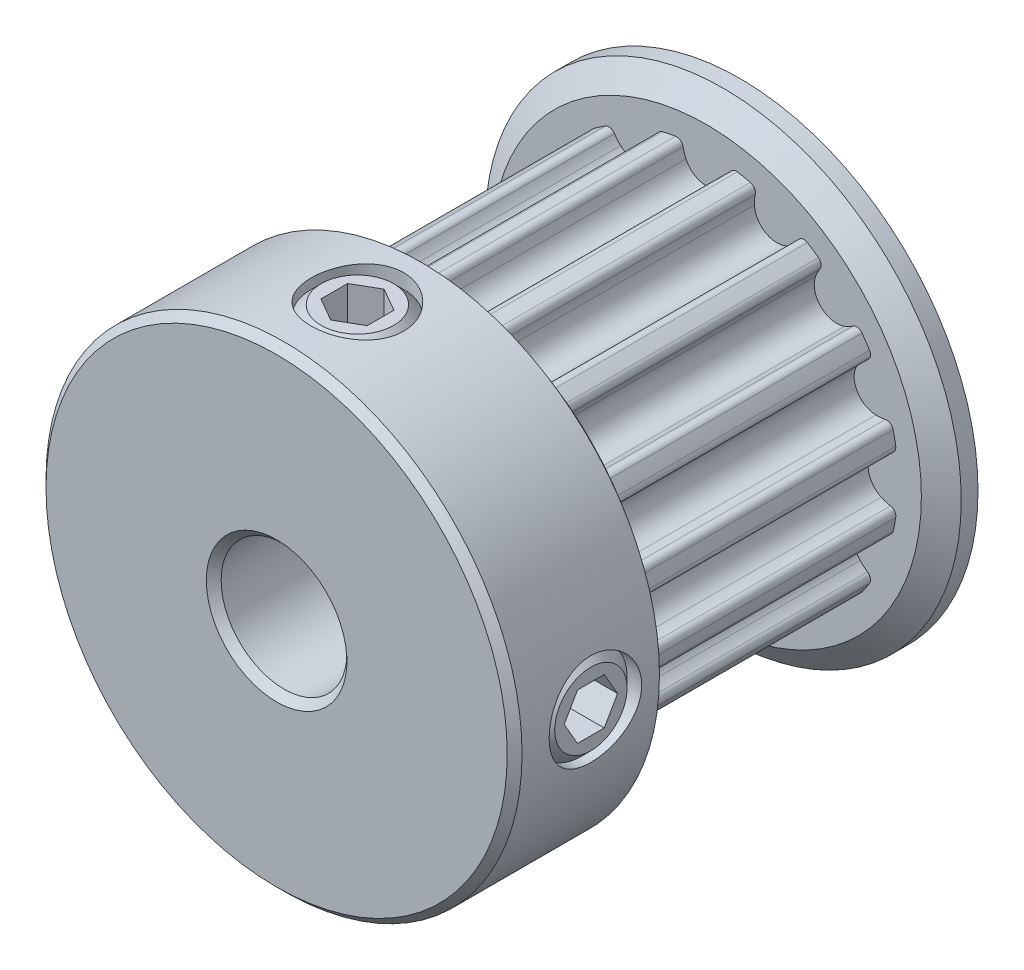
SolidWorks part; units mm, degrees
ref_plane "Front Plane" through (0, 0, 0) normal (0, 0, 1) x (1, 0, 0)
ref_plane "Top Plane" through (0, 0, 0) normal (0, 1, 0) x (1, 0, 0)
ref_plane "Right Plane" through (0, 0, 0) normal (1, 0, 0) x (0, 0, -1)
sketch "Sketch1" plane through (0, 0, 0) normal (0, 0, 1) x (1, 0, 0)
  line L1 (-2.553, 6.1245) -> (2.553, 6.1245) construction
  line L4 (0, 0) -> (0, 6.1245) construction
  line L5 (0, 6.1245) -> (0, 12.0266) construction
  line L6 (0, 7.6455) -> (2.9417, 7.0569) construction
  line L7 (2.9417, 7.0569) -> (3.8741, 6.6682) construction
  line L8 (2.9417, 7.0569) -> (2.553, 6.1245) construction
  line L9 (-2.9417, 7.0569) -> (-2.553, 6.1245) construction
  line L10 (-2.7951, 6.7052) -> (-3.7579, 9.015)
  line L11 (-3.7579, 9.015) -> (3.7579, 9.015)
  line L12 (3.7579, 9.015) -> (2.7951, 6.7052)
  circle A0 centre (0, 0) radius 7.6455 construction
  circle A1 centre (0, 0) radius 9.015 construction
  circle A2 centre (0, 0) radius 7.2645 construction
  arc A3 (-0.7739, 6.6229) -> (0.7739, 6.6229) centre (0, 6.9745) ccw
  arc A4 (-0.7739, 6.6229) -> (-0.8836, 6.9694) centre (0.61, 7.2516) cw
  arc A5 (-2.7951, 6.7052) -> (-1.1695, 7.1697) centre (0, 0) cw
  arc A6 (-0.8836, 6.9694) -> (-1.1695, 7.1697) centre (-1.1292, 6.923) ccw
  arc A7 (2.7951, 6.7052) -> (1.1695, 7.1697) centre (0, 0) ccw
  arc A8 (0.8836, 6.9694) -> (1.1695, 7.1697) centre (1.1292, 6.923) cw
  arc A9 (0.7739, 6.6229) -> (0.8836, 6.9694) centre (-0.61, 7.2516) ccw
  point P6 (0, 20.9083)
  point P11 (0, 7.6455)
  point P13 (0, 9.015)
  point P14 (0, 7.2645)
  dimension "D1" = 8.8817
  dimension "D2" = 4.3811
sketch "Sketch2" plane through (0, 0, 0) normal (1, 0, 0) x (0, 0, -1)
  line L0 (-8.775, 2.3812) -> (8.775, 2.3812)
  line L1 (-8.775, 2.3812) -> (-8.775, 9.015)
  line L2 (-3.29, 9.015) -> (-8.775, 9.015)
  line L3 (-3.925, 2.3813) -> (-3.925, 9.015) construction
  line L4 (-3.925, 9.015) -> (-2.655, 9.015) construction
  line L5 (-2.655, 9.015) -> (-2.655, 7.2645) construction
  line L6 (-2.655, 7.2645) -> (7.505, 7.2645)
  line L7 (7.505, 7.2645) -> (7.505, 9.015) construction
  line L8 (7.505, 9.015) -> (8.775, 9.015) construction
  line L9 (8.775, 9.015) -> (8.775, 2.3812)
  line L10 (-8.775, 0) -> (8.775, 0) construction
  line L11 (8.14, 9.015) -> (7.505, 8.1398)
  line L12 (-2.655, 8.1398) -> (-3.29, 9.015)
  line L14 (-2.655, 8.1398) -> (-2.655, 7.2645)
  line L15 (7.505, 7.2645) -> (7.505, 8.1398)
  line L16 (8.14, 9.015) -> (8.775, 9.015)
  arc A0 (-2.655, 8.1398) -> (-3.29, 9.015) centre (-3.5757, 8.1398) ccw construction
  arc A1 (7.505, 8.1398) -> (8.14, 9.015) centre (8.4257, 8.1398) cw construction
  point P12 (-2.655, 8.1398)
  point P14 (-3.29, 9.015)
  point P20 (7.505, 8.1398)
  point P21 (8.14, 9.015)
  point P25 (7.505, 0)
  point P26 (-2.655, 0)
  dimension "OA" = 17.55
  dimension "Bore" = 4.7625
  dimension "Outside Width" = 11.43
  dimension "Inside Width" = 10.16
revolve "Revolve1" add sketch "Sketch2" angle 360 mid plane about L10
sketch "Sketch3" plane through (0, 0, 0) normal (0, 0, 1) x (1, 0, 0)
  line L6 (3.7579, 9.015) -> (-3.7579, 9.015)
  line L7 (2.7951, 6.7052) -> (3.7579, 9.015)
  line L8 (-3.7579, 9.015) -> (-2.7951, 6.7052)
  line L9 (3.7579, 9.015) -> (-3.7579, 9.015)
  line L10 (2.7951, 6.7052) -> (3.7579, 9.015)
  line L11 (-3.7579, 9.015) -> (-2.7951, 6.7052)
  arc A8 (2.7951, 6.7052) -> (1.1695, 7.1697) centre (0, 0) ccw
  arc A9 (1.1695, 7.1697) -> (0.8836, 6.9694) centre (1.1292, 6.923) ccw
  arc A10 (0.7739, 6.6229) -> (0.8836, 6.9694) centre (-0.61, 7.2516) ccw
  arc A11 (-0.7739, 6.6229) -> (0.7739, 6.6229) centre (0, 6.9745) ccw
  arc A12 (-0.8836, 6.9694) -> (-0.7739, 6.6229) centre (0.61, 7.2516) ccw
  arc A13 (-0.8836, 6.9694) -> (-1.1695, 7.1697) centre (-1.1292, 6.923) ccw
  arc A14 (-1.1695, 7.1697) -> (-2.7951, 6.7052) centre (0, 0) ccw
  arc A15 (2.7951, 6.7052) -> (1.1695, 7.1697) centre (0, 0) ccw
  arc A16 (1.1695, 7.1697) -> (0.8836, 6.9694) centre (1.1292, 6.923) ccw
  arc A17 (0.7739, 6.6229) -> (0.8836, 6.9694) centre (-0.61, 7.2516) ccw
  arc A18 (-0.7739, 6.6229) -> (0.7739, 6.6229) centre (0, 6.9745) ccw
  arc A19 (-0.8836, 6.9694) -> (-0.7739, 6.6229) centre (0.61, 7.2516) ccw
  arc A20 (-0.8836, 6.9694) -> (-1.1695, 7.1697) centre (-1.1292, 6.923) ccw
  arc A21 (-1.1695, 7.1697) -> (-2.7951, 6.7052) centre (0, 0) ccw
  dimension "D1" = 0
extrude "Cut-Extrude1" cut sketch "Sketch3" against normal up to vertex (7.505 mm away) from vertex up to point (0, 7.2645, -7.505) starting at point (0, 7.2645, 2.655)
pattern_circular "CirPattern1" count 16 over 360 about axis through (0, 0, 8.775) along (0, 0, 1) of "Cut-Extrude1"
sketch "Sketch4" plane through (0, 0, 0) normal (1, 0, 0) x (0, -1, 0)
  line L0 (0, -2.655) -> (0, -8.775) construction
  line L1 (-2.3812, -8.775) -> (2.3812, -8.775) construction
  line L2 (8.1398, -2.655) -> (-8.1398, -2.655) construction
  circle A0 centre (0, -5.715) radius 1.7526
extrude "Cut-Extrude2" cut sketch "Sketch4" along normal through all
ref_plane "Plane1" through (0, 0, 5.715) normal (0, 0, 1) x (1, 0, 0)
sketch "Sketch5" plane through (0, 0, 5.715) normal (0, 0, 1) x (1, 0, 0)
  line L0 (0, 0) -> (0, 9.015) construction
  line L1 (2.3812, -1.3716) -> (2.3812, 0)
  line L2 (2.7622, -1.7526) -> (8.462, -1.7526)
  line L3 (2.3812, 0) -> (9.015, 0) construction
  line L4 (2.3812, 0) -> (8.843, 0)
  line L5 (8.843, 0) -> (8.843, -1.3716)
  line L6 (2.7622, -1.7526) -> (2.3812, -1.3716)
  line L7 (8.843, -1.3716) -> (8.462, -1.7526)
  circle A0 centre (0, 0) radius 9.015 construction
  circle A1 centre (0, 0) radius 2.3812 construction
  point P2 (2.3812, -1.7526)
  point P11 (8.843, -1.7526)
revolve "Revolve2" add sketch "Sketch5" angle 360 mid plane about L4
sketch "Sketch6" plane through (8.843, 5.3841, 0) normal (-1, 0, 0) x (0, -1, 0)
  line L1 (5.3841, 6.7269) -> (4.5078, 6.2209)
  line L2 (4.5078, 6.2209) -> (4.5078, 5.2091)
  line L3 (4.5078, 5.2091) -> (5.3841, 4.7031)
  line L4 (5.3841, 4.7031) -> (6.2604, 5.2091)
  line L5 (6.2604, 5.2091) -> (6.2604, 6.2209)
  line L6 (6.2604, 6.2209) -> (5.3841, 6.7269)
  circle A0 centre (5.3841, 5.715) radius 0.8763 construction
  dimension "D1" = 1.7526
extrude "Cut-Extrude3" cut sketch "Sketch6" along normal blind 1.3144
pattern_circular "CirPattern3" count 2 over 90 about axis through (0, 0, 8.775) along (0, 0, 1) of "Cut-Extrude2", "Revolve2", "Cut-Extrude3"
chamfer "Chamfer1" distance 0.2807 angle 45 2 edges at (2.3812, 0, 8.775) (9.015, 0, 8.775)
ref_axis "Center Axis 1" through (0, 0, -8.775) along (0, 0, 1)
ref_plane "Contact Plane 1" through (0, 0, 8.775) normal (0, 0, 1) x (1, 0, 0)
ref_plane "Contact Plane 2" through (0, 0, -8.775) normal (0, 0, -1) x (-1, 0, 0)
equation "\"D2@Sketch1\"= \"D1@Sketch1\" / 2"
equation "\"D1@Sketch6\" = \"Set Screw@Sketch4\" / 2"
equation "\"D1@Cut-Extrude3\" = \"D1@Sketch6\"*.75"
